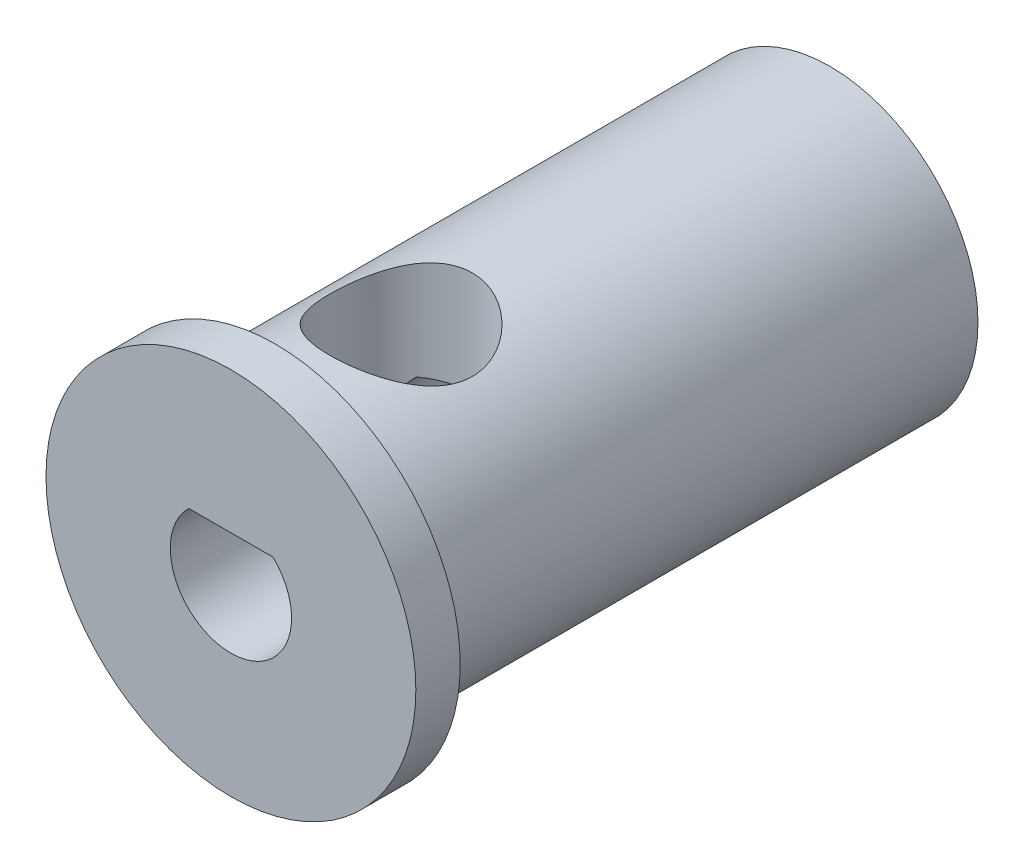
SolidWorks part; units mm, degrees
material "PLA2"
ref_plane "Front Plane" through (0, 0, 0) normal (0, 0, 1) x (1, 0, 0)
ref_plane "Top Plane" through (0, 0, 0) normal (0, 1, 0) x (1, 0, 0)
ref_plane "Right Plane" through (0, 0, 0) normal (1, 0, 0) x (0, 0, -1)
sketch "Sketch2" plane through (0, 0, 0) normal (0, 0, 1) x (1, 0, 0)
  circle A1 centre (0, 0) radius 5.08
  circle A2 centre (0, 0) radius 2.0828
  dimension "D1" = 4.1656
  dimension "D3" = 10.16
extrude "Boss-Extrude1" add sketch "Sketch2" along normal blind 19.05
sketch "Sketch6" plane through (0, 0, 0) normal (0, 0, -1) x (-1, 0, 0)
  line L1 (1.4465, 1.4986) -> (-1.4465, 1.4986)
  line L2 (0, 1.4986) -> (0, -2.0828) construction
  arc A3 (1.4465, 1.4986) -> (-1.4465, 1.4986) centre (0, 0) ccw
  circle A4 centre (0, 0) radius 2.0828 construction
  dimension "D1" = 3.5814
extrude "Boss-Extrude2" add sketch "Sketch6" against normal up to surface (19.05 mm away) up to face at (5.08, 0, 19.05)
sketch "Sketch3" plane through (0, 0, 0) normal (0, -1, 0) x (1, 0, 0)
  line L0 (0, 14.732) -> (0, 0) construction
  line L1 (-5.08, 9.525) -> (5.08, 9.525) construction
  line L2 (-5.08, 19.05) -> (-5.08, 0) construction
  line L3 (5.08, 0) -> (5.08, 19.05) construction
  line L4 (5.08, 19.05) -> (-5.08, 19.05) construction
  circle A0 centre (0, 14.732) radius 2.4511
  dimension "D1" = 4.9022
  dimension "D2" = 4.318
extrude "Cut-Extrude1" cut sketch "Sketch3" against normal blind 25.4
sketch "Sketch4" plane through (0, 0, 0) normal (1, 0, 0) x (0, 0, -1)
  line L1 (0, 0) -> (50000, 0) construction
  line L2 (-19.05, 0) -> (-19.05, 6.35)
  line L3 (-19.05, 6.35) -> (-20.574, 6.35)
  line L4 (-20.574, 6.35) -> (-20.574, 0)
  line L5 (-20.574, 0) -> (-19.05, 0)
  line L6 (-19.05, 5.08) -> (-19.05, -5.08) construction
  dimension "D1" = 1.524
  dimension "D2" = 12.7
revolve "Revolve1" add sketch "Sketch4" angle 360 about L1
sketch "Sketch5" plane through (0, 0, 19.05) normal (0, 0, -1) x (-1, 0, 0)
  line L1 (1.4465, 1.4986) -> (-1.4465, 1.4986)
  line L2 (1.4465, 1.4986) -> (-1.4465, 1.4986)
  arc A1 (-1.4465, 1.4986) -> (1.4465, 1.4986) centre (0, 0) ccw
  arc A2 (-1.4465, 1.4986) -> (1.4465, 1.4986) centre (0, 0) ccw
  dimension "D1" = 0
extrude "Cut-Extrude2" cut sketch "Sketch5" against normal through all
